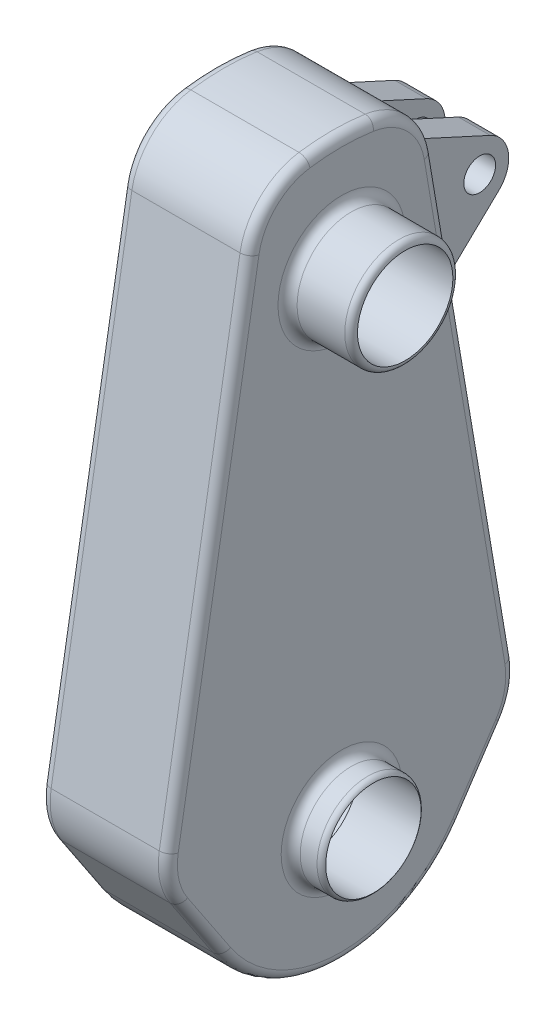
SolidWorks part; units mm, degrees
ref_plane "前视基准面" through (0, 0, 0) normal (0, 0, 1) x (1, 0, 0)
ref_plane "上视基准面" through (0, 0, 0) normal (0, 1, 0) x (1, 0, 0)
ref_plane "右视基准面" through (0, 0, 0) normal (1, 0, 0) x (0, 0, -1)
sketch "草图1" plane through (0, 0, 0) normal (1, 0, 0) x (0, 0, -1)
  line L0 (0, 0) -> (0, 150) construction
  line L1 (-55.7892, 8.5385) -> (-31.7802, 150.5691)
  line L3 (-55.7892, 8.5385) -> (-37.4423, -18.982)
  line L4 (0, 0) -> (48.4243, 149.0347) construction
  line L6 (55.7892, 8.5385) -> (37.4423, -18.982)
  line L7 (55.7892, 8.5385) -> (31.7802, 150.5691)
  line L8 (-26, 150) -> (-45, 7.5)
  line L9 (45, 7.5) -> (29.1218, -16.3174)
  line L10 (-26, 150) -> (-22.6959, 174.7807)
  line L11 (26, 150) -> (45, 7.5)
  line L12 (-45, 7.5) -> (-29.1218, -16.3174)
  line L14 (48.4243, 149.0347) -> (32.4948, 146.3419) construction
  line L15 (32.4948, 146.3419) -> (65.103, 151.8541) construction
  line L16 (-31.7802, 150.5691) -> (-26.6133, 181.1354)
  line L23 (31.7802, 150.5691) -> (26.6133, 181.1354)
  line L26 (26, 150) -> (22.6959, 174.7807)
  line L27 (65.103, 151.8541) -> (36.2429, 124.1695) construction
  line L28 (54.49, 141.6733) -> (36.2429, 124.1695)
  line L29 (51.7333, 157.9808) -> (28.7467, 168.5144)
  line L30 (28.7467, 168.5144) -> (36.2429, 124.1695)
  circle A0 centre (0, 0) radius 15
  circle A1 centre (0, 150) radius 15
  circle A2 centre (48.4243, 149.0347) radius 5
  arc A4 (37.4423, -18.982) -> (-37.4423, -18.982) centre (0, 5.9795) cw
  arc A5 (-22.6959, 174.7807) -> (22.6959, 174.7807) centre (0, 123.4205) cw
  arc A6 (29.1218, -16.3174) -> (-29.1218, -16.3174) centre (0, 3.0971) cw
  arc A9 (51.7333, 157.9808) -> (54.49, 141.6733) centre (47.5674, 148.8898) cw
  arc A10 (-26.6133, 181.1354) -> (26.6133, 181.1354) centre (0, 113.4462) cw
  point P15 (0, 200)
  point P18 (0, -75.1454)
  point P43 (0, 229.5525)
  dimension "D2" = 45
  dimension "D4" = 35
  dimension "D5" = 10
extrude "凸台-拉伸1" add sketch "草图1" along normal blind 10 contours L1 L16 A10 L23 L7 L6 A4 L3
ref_plane "基准面1" through (20, 0, 0) normal (1, 0, 0) x (0, 0, -1)
extrude "凸台-拉伸2" add sketch "草图1<5>" along normal blind 10 from offset 30 separate body contours L3 A4 L6 L7 L23 A10 L16 L1 | A1 | A0
sketch "草图1<5>" plane through (0, 0, 0) normal (1, 0, 0) x (0, 0, -1) same geometry as "草图1"
extrude "凸台-拉伸3" add sketch "草图1<6>" along normal blind 20 from offset 10 contours A4 L6 L7 L1 L3 L9 A6 L12 region at (0, 79.1349, 41.3066)
sketch "草图1<6>" plane through (0, 0, 0) normal (1, 0, 0) x (0, 0, -1) same geometry as "草图1"
extrude "凸台-拉伸4" add sketch "草图1<7>" along normal blind 10 from offset 5 contours A9 L7 A2 region at (0, 147.8513, -41.4238)
sketch "草图1<7>" plane through (0, 0, 0) normal (1, 0, 0) x (0, 0, -1) same geometry as "草图1"
mirror "镜向2" about plane through (20, 0, 0) normal (1, 0, 0) of "凸台-拉伸4"
sketch "草图2" plane through (40, 0, 0) normal (1, 0, 0) x (0, 0, -1)
  circle A0 centre (0, 150) radius 17
  circle A1 centre (0, 0) radius 16
  circle M2 centre (0, 150) radius 15
  circle M11 centre (0, 0) radius 15
extrude "凸台-拉伸5" add sketch "草图2" along normal blind 20 contours A0 M2 region at (40, 150, 16.5192)
extrude "凸台-拉伸6" add sketch "草图2<3>" along normal blind 10 contours A1 M11 region at (40, 0, 15.5475)
sketch "草图2<3>" plane through (40, 0, 0) normal (1, 0, 0) x (0, 0, -1) same geometry as "草图2"
fillet "圆角1" radius 2 1 edges at (60, 150, -17)
fillet "圆角2" radius 2 1 edges at (50, 0, -16)
fillet "圆角3" radius 22 4 edges at (20, 8.5385, -55.7892) (20, 8.5385, 55.7892) (20, 181.1354, -26.6133) (20, 181.1354, 26.6133)
fillet "圆角4" radius 3 10 edges at (0, 92.2351, 41.6411) (0, 8.8868, 54.1575) (0, -8.8533, 44.1947) (0, -39.0205, 0) (0, -8.8533, -44.1947) (0, 8.8868, -54.1575) (0, 92.2351, -41.6411) (0, 186.1793, 0) (0, 179.3993, 22.6245) (0, 179.3993, -22.6245)
fillet "圆角5" radius 3 12 edges at (40, -39.0205, 0) (40, -8.8533, 44.1947) (40, 8.8868, 54.1575) (40, 92.2351, 41.6411) (40, 92.2351, -41.6411) (40, 8.8868, -54.1575) (40, -8.8533, -44.1947) (40, 150, 17) (40, 0, 16) (40, 186.1793, 0) (40, 179.3993, 22.6245) (40, 179.3993, -22.6245)
